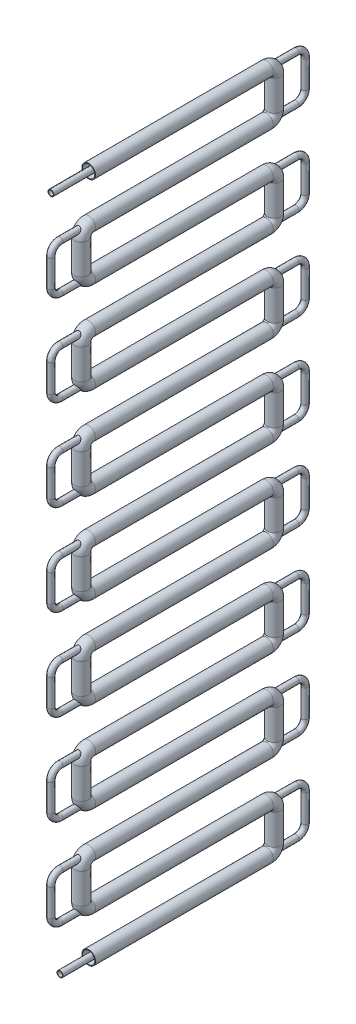
SolidWorks part; units mm, degrees
ref_plane "Alzado" through (0, 0, 0) normal (0, 0, 1) x (1, 0, 0)
ref_plane "Planta" through (0, 0, 0) normal (0, 1, 0) x (1, 0, 0)
ref_plane "Vista lateral" through (0, 0, 0) normal (1, 0, 0) x (0, 0, -1)
sketch "Seccion agua" plane through (0, 0, 0) normal (0, 0, 1) x (1, 0, 0)
  circle A2 centre (0, 0) radius 8
  circle A3 centre (0, 0) radius 9
  dimension "D1" = 16
  dimension "D2" = 1
sketch "Recorrido agua" plane through (0, 0, 0) normal (1, 0, 0) x (0, 0, -1)
  line L0 (0, 0) -> (235, 0)
  line L1 (245, -10) -> (245, -50)
  line L2 (235, -60) -> (0, -60)
  line L3 (-10, -70) -> (-10, -110)
  line L4 (0, -120) -> (235, -120)
  line L5 (0, 0) -> (0, -100.3636) construction
  line L6 (235, 0) -> (235, -103.1636) construction
  line L7 (245, -130) -> (245, -170)
  line L8 (235, -180) -> (0, -180)
  line L9 (-10, -190) -> (-10, -230)
  line L10 (0, -240) -> (235, -240)
  line L11 (245, -250) -> (245, -290)
  line L12 (235, -300) -> (0, -300)
  line L13 (-10, -310) -> (-10, -350)
  line L14 (0, -360) -> (235, -360)
  line L15 (245, -370) -> (245, -410)
  line L16 (235, -420) -> (0, -420)
  line L17 (-10, -430) -> (-10, -470)
  line L18 (0, -480) -> (235, -480)
  line L19 (245, -490) -> (245, -530)
  line L20 (235, -540) -> (0, -540)
  line L21 (-10, -550) -> (-10, -590)
  line L22 (0, -600) -> (235, -600)
  line L23 (245, -610) -> (245, -650)
  line L24 (235, -660) -> (0, -660)
  line L25 (-10, -670) -> (-10, -710)
  line L26 (0, -720) -> (235, -720)
  line L27 (245, -730) -> (245, -770)
  line L28 (235, -780) -> (0, -780)
  line L29 (-10, -790) -> (-10, -830)
  line L30 (0, -840) -> (235, -840)
  line L31 (245, -850) -> (245, -890)
  line L32 (235, -900) -> (0, -900)
  line L35 (0, -960) -> (235, -960) [skipped]
  line L36 (-10, -910) -> (-10, -950) [skipped]
  arc A0 (235, 0) -> (245, -10) centre (235, -10) cw
  arc A1 (245, -50) -> (235, -60) centre (235, -50) cw
  arc A2 (0, -60) -> (-10, -70) centre (0, -70) ccw
  arc A3 (-10, -110) -> (0, -120) centre (0, -110) ccw
  arc A4 (245, -170) -> (235, -180) centre (235, -170) cw
  arc A5 (0, -180) -> (-10, -190) centre (0, -190) ccw
  arc A6 (235, -120) -> (245, -130) centre (235, -130) cw
  arc A7 (-10, -230) -> (0, -240) centre (0, -230) ccw
  arc A8 (245, -290) -> (235, -300) centre (235, -290) cw
  arc A9 (0, -300) -> (-10, -310) centre (0, -310) ccw
  arc A10 (235, -240) -> (245, -250) centre (235, -250) cw
  arc A11 (-10, -350) -> (0, -360) centre (0, -350) ccw
  arc A12 (245, -410) -> (235, -420) centre (235, -410) cw
  arc A13 (0, -420) -> (-10, -430) centre (0, -430) ccw
  arc A14 (235, -360) -> (245, -370) centre (235, -370) cw
  arc A15 (-10, -470) -> (0, -480) centre (0, -470) ccw
  arc A16 (245, -530) -> (235, -540) centre (235, -530) cw
  arc A17 (0, -540) -> (-10, -550) centre (0, -550) ccw
  arc A18 (235, -480) -> (245, -490) centre (235, -490) cw
  arc A19 (-10, -590) -> (0, -600) centre (0, -590) ccw
  arc A20 (245, -650) -> (235, -660) centre (235, -650) cw
  arc A21 (0, -660) -> (-10, -670) centre (0, -670) ccw
  arc A22 (235, -600) -> (245, -610) centre (235, -610) cw
  arc A23 (-10, -710) -> (0, -720) centre (0, -710) ccw
  arc A24 (245, -770) -> (235, -780) centre (235, -770) cw
  arc A25 (0, -780) -> (-10, -790) centre (0, -790) ccw
  arc A26 (235, -720) -> (245, -730) centre (235, -730) cw
  arc A27 (-10, -830) -> (0, -840) centre (0, -830) ccw
  arc A28 (245, -890) -> (235, -900) centre (235, -890) cw
  arc A30 (235, -840) -> (245, -850) centre (235, -850) cw
  arc A32 (-10, -950) -> (0, -960) centre (0, -950) ccw [skipped]
  arc A33 (0, -900) -> (-10, -910) centre (0, -910) ccw [skipped]
  dimension "D1" = 10
  dimension "D2" = 60
  dimension "D3" = 235
  dimension "D4" = 8
sweep "Tuberia agua" add profiles "Seccion agua" path "Recorrido agua"
ref_plane "Plano refrigerante" through (0, 0, 50) normal (0, 0, 1) x (1, 0, 0)
sketch "Seccion refrigerante" plane through (0, 0, 50) normal (0, 0, 1) x (1, 0, 0)
  circle A0 centre (0, 0) radius 3.175
  circle A1 centre (0, 0) radius 3.975
  dimension "D1" = 0.8
  dimension "D2" = 6.35
sketch "Recorrido refrigerante" plane through (0, 0, 0) normal (1, 0, 0) x (0, 0, -1)
  line L0 (-50, 0) -> (274, 0)
  line L1 (-50, 3.975) -> (-50, -3.975) construction
  line L2 (286, -12) -> (286, -48)
  line L3 (274, -60) -> (-38, -60)
  line L4 (-50, 9.68) -> (-50, -9.68) construction
  line L5 (-50, -72) -> (-50, -108)
  line L6 (-38, -120) -> (274, -120)
  line L7 (274, -12) -> (274, -94.7312) construction
  line L8 (286, -132) -> (286, -168)
  line L10 (274, -180) -> (-38, -180)
  line L11 (-38, -240) -> (274, -240)
  line L12 (-50, -192) -> (-50, -228)
  line L13 (286, -252) -> (286, -288)
  line L14 (274, -300) -> (-38, -300)
  line L15 (-38, -360) -> (274, -360)
  line L16 (-50, -312) -> (-50, -348)
  line L17 (286, -372) -> (286, -408)
  line L18 (274, -420) -> (-38, -420)
  line L19 (-38, -480) -> (274, -480)
  line L20 (-50, -432) -> (-50, -468)
  line L21 (286, -492) -> (286, -528)
  line L22 (274, -540) -> (-38, -540)
  line L23 (-38, -600) -> (274, -600)
  line L24 (-50, -552) -> (-50, -588)
  line L25 (286, -612) -> (286, -648)
  line L26 (274, -660) -> (-38, -660)
  line L27 (-38, -720) -> (274, -720)
  line L28 (-50, -672) -> (-50, -708)
  line L29 (286, -732) -> (286, -768)
  line L30 (274, -780) -> (-38, -780)
  line L31 (-38, -840) -> (274, -840)
  line L32 (-50, -792) -> (-50, -828)
  line L33 (286, -852) -> (286, -888)
  line L34 (274, -900) -> (-38, -900)
  line L35 (236, -10) -> (236, -50) construction
  line L37 (-38, -960) -> (274, -960) [skipped]
  line L38 (-50, -912) -> (-50, -948) [skipped]
  arc A0 (274, 0) -> (286, -12) centre (274, -12) cw
  arc A1 (286, -48) -> (274, -60) centre (274, -48) cw
  arc A2 (-38, -60) -> (-50, -72) centre (-38, -72) ccw
  arc A3 (-50, -108) -> (-38, -120) centre (-38, -108) ccw
  arc A4 (274, -120) -> (286, -132) centre (274, -132) cw
  arc A5 (286, -168) -> (274, -180) centre (274, -168) cw
  arc A6 (-38, -180) -> (-50, -192) centre (-38, -192) ccw
  arc A7 (-50, -228) -> (-38, -240) centre (-38, -228) ccw
  arc A8 (274, -240) -> (286, -252) centre (274, -252) cw
  arc A9 (286, -288) -> (274, -300) centre (274, -288) cw
  arc A10 (-38, -300) -> (-50, -312) centre (-38, -312) ccw
  arc A11 (-50, -348) -> (-38, -360) centre (-38, -348) ccw
  arc A12 (274, -360) -> (286, -372) centre (274, -372) cw
  arc A13 (286, -408) -> (274, -420) centre (274, -408) cw
  arc A14 (-38, -420) -> (-50, -432) centre (-38, -432) ccw
  arc A15 (-50, -468) -> (-38, -480) centre (-38, -468) ccw
  arc A16 (274, -480) -> (286, -492) centre (274, -492) cw
  arc A17 (286, -528) -> (274, -540) centre (274, -528) cw
  arc A18 (-38, -540) -> (-50, -552) centre (-38, -552) ccw
  arc A19 (-50, -588) -> (-38, -600) centre (-38, -588) ccw
  arc A20 (274, -600) -> (286, -612) centre (274, -612) cw
  arc A21 (286, -648) -> (274, -660) centre (274, -648) cw
  arc A22 (-38, -660) -> (-50, -672) centre (-38, -672) ccw
  arc A23 (-50, -708) -> (-38, -720) centre (-38, -708) ccw
  arc A24 (274, -720) -> (286, -732) centre (274, -732) cw
  arc A25 (286, -768) -> (274, -780) centre (274, -768) cw
  arc A26 (-38, -780) -> (-50, -792) centre (-38, -792) ccw
  arc A27 (-50, -828) -> (-38, -840) centre (-38, -828) ccw
  arc A28 (274, -840) -> (286, -852) centre (274, -852) cw
  arc A29 (286, -888) -> (274, -900) centre (274, -888) cw
  arc A32 (-50, -948) -> (-38, -960) centre (-38, -948) ccw [skipped]
  arc A33 (-38, -900) -> (-50, -912) centre (-38, -912) ccw [skipped]
  dimension "D1" = 12
  dimension "D4" = 8
  dimension "D2" = 60
  dimension "D3" = 50
sweep "Tuberia refrigerante" add profiles "Seccion refrigerante" path "Recorrido refrigerante"
